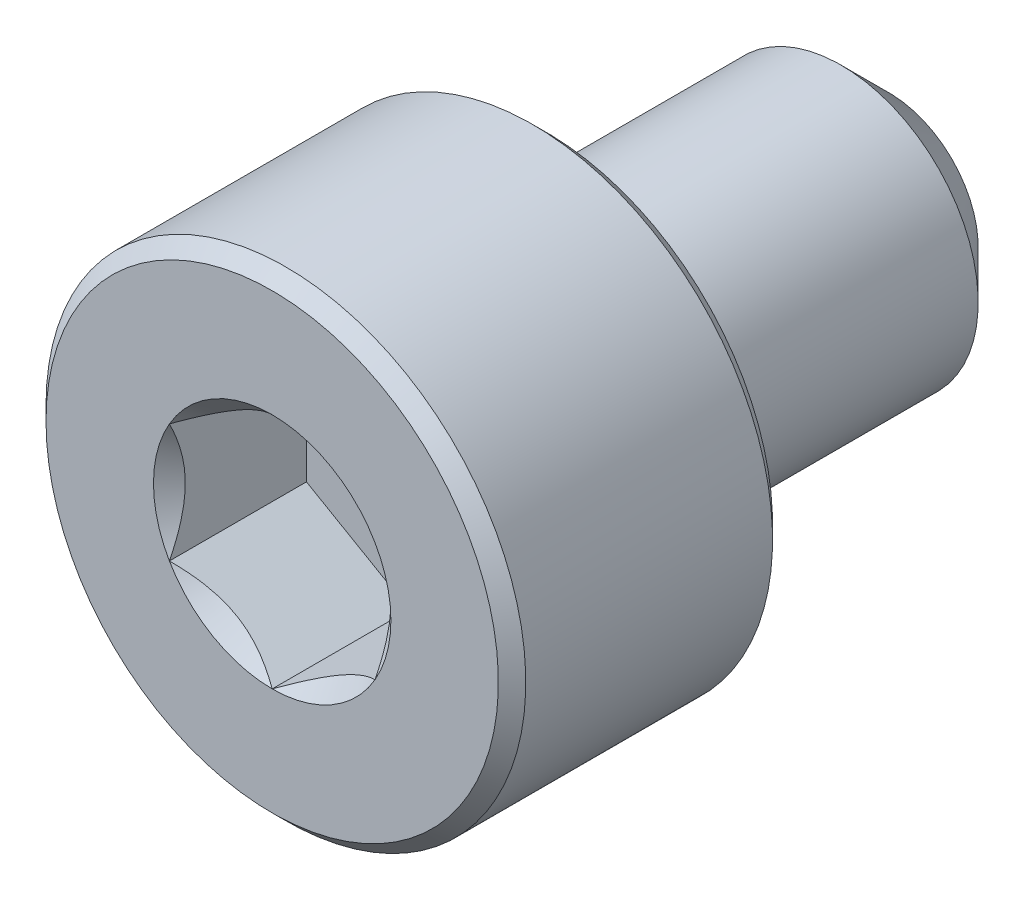
SolidWorks part; units mm, degrees
material "Alloy Steel"
ref_plane "Front Plane" through (0, 0, 0) normal (0, 0, 1) x (1, 0, 0)
ref_plane "Top Plane" through (0, 0, 0) normal (0, 1, 0) x (1, 0, 0)
ref_plane "Right Plane" through (0, 0, 0) normal (1, 0, 0) x (0, 0, -1)
sketch "Sketch1" plane through (0, 0, 0) normal (1, 0, 0) x (0, 0, -1)
  line L0 (-4.5, 0) -> (4.5, 0) construction
  line L1 (4.5, 0) -> (4.5, 1.3) construction
  line L2 (4.5, 1.3) -> (3.8, 2) construction
  line L3 (3.8, 2) -> (-0.5, 2) construction
  line L5 (-0.5, 2) -> (-0.5, 3.5) construction
  line L6 (-0.5, 3.5) -> (-4.5, 3.5) construction
  line L7 (-4.5, 3.5) -> (-4.5, 0) construction
  line L8 (4.5, 1.3) -> (4.5, 2) construction
  line L9 (4.4563, 2.0758) -> (4.8063, 1.4696) construction
  line L10 (4.8063, 1.4696) -> (5.1563, 2.0758) construction
  line L11 (5.1563, 2.0758) -> (4.4563, 2.0758) construction
  line L12 (4.8063, 2.0758) -> (4.8063, 2) construction
  line L13 (4.8063, 1.4696) -> (4.8063, 1.5453) construction
  line L14 (4.7625, 1.5453) -> (4.85, 1.5453) construction
  line L15 (4.5, 2) -> (5.1125, 2) construction
  line L16 (4.4781, 2.0379) -> (5.1344, 2.0379) construction
  line L17 (4.5, 0) -> (4.5, -2) construction
  line L18 (-0.7, 3.5) -> (-0.5, 3.3) construction
  line L19 (-4.3, 3.5) -> (-4.5, 3.3) construction
  point P0 (-4.5, 1.5)
  point P3 (2.05, 2)
  point P4 (0, 0)
  point P22 (4.8063, 1.5453)
  point P24 (-0.5, 2)
  point P25 (4.8063, 2)
  point P28 (4.8063, 2.0379)
  point P29 (2.05, -2)
  point P31 (-2.5, 3.5)
  point P37 (-1.2, 3.5)
  point P38 (-4.2, 3.5)
  point P41 (-2.5, 0)
  dimension "head height" = 4
  dimension "D1" = 45
  dimension "Head Diameter" = 7
  dimension "Thread Size" = 4
  dimension "drive size" = 3
  dimension "Thread Pitch" = 0.7
  dimension "D2" = 0.0875
  dimension "D3" = 0.7
  dimension "D4" = 2.45
  dimension "D7" = 0.2
  dimension "D8" = 0.2
  dimension "D9" = 0.2
  dimension "D10" = 0.1
  dimension "D11" = 0.5
  dimension "length" = 5
  dimension "Drive Depth" = 2
sketch "Sketch2" plane through (0, 0, 0) normal (1, 0, 0) x (0, 0, -1)
  line L1 (-4.3, 3.5) -> (-0.7, 3.5)
  line L4 (3.8, 2) -> (4.5, 1.3)
  line L5 (4.5, 1.3) -> (4.5, 0)
  line L6 (-0.7, 3.5) -> (-0.5, 3.3) construction
  line L7 (4.5, 0) -> (-4.5, 0)
  line L8 (-4.3, 3.5) -> (-4.5, 3.3) construction
  line L9 (-0.7, 3.5) -> (-0.5, 3.3)
  line L10 (-4.3, 3.5) -> (-4.5, 3.3)
  line L11 (-4.5, 3.3) -> (-4.5, 0)
  line L12 (-0.5, 3.3) -> (-0.5, 2)
  line L13 (-0.5, 2) -> (3.8, 2)
revolve "Revolve1" add sketch "Sketch2" angle 360 about L7
sketch "Sketch3" plane through (0, 0, 4.5) normal (0, 0, 1) x (1, 0, 0)
  line L1 (0, 1.7321) -> (-1.5, 0.866)
  line L2 (-1.5, 0.866) -> (-1.5, -0.866)
  line L3 (-1.5, -0.866) -> (0, -1.7321)
  line L4 (0, -1.7321) -> (1.5, -0.866)
  line L5 (1.5, -0.866) -> (1.5, 0.866)
  line L6 (1.5, 0.866) -> (0, 1.7321)
  circle A0 centre (0, 0) radius 1.5 construction
  dimension "D1" = 3
extrude "Cut-Extrude1" cut sketch "Sketch3" against normal up to vertex (2 mm away) up to point (0, 0, 2.5)
sketch "Sketch4" plane through (0, 0, 4.5) normal (0, 0, 1) x (1, 0, 0)
  circle A0 centre (0, 0) radius 1.7321
extrude "Cut-Extrude2" cut sketch "Sketch4" against normal blind 0.5 draft 45
ref_plane "Plane1" [suppressed] through (0, 0, 0.5) normal (0, 0, 1) x (1, 0, 0)
split "Split1" [suppressed] bodies to split 106
sketch "Sketch6" [suppressed] plane through (0, 0, -4.5) normal (0, 0, -1) x (-1, 0, 0)
  circle A0 centre (0, 0) radius 2
curve "Helix/Spiral1" [suppressed] pitch 0.7 height 5.7 turns 8.1429
sketch "Sketch7" [suppressed] plane through (0, 0, 0) normal (1, 0, 0) x (0, 0, -1)
  line L0 (4.4781, 2.0379) -> (5.1344, 2.0379)
  line L1 (5.1344, 2.0379) -> (4.85, 1.5453)
  line L2 (4.85, 1.5453) -> (4.7625, 1.5453)
  line L3 (4.7625, 1.5453) -> (4.4781, 2.0379)
sweep "Cut-Sweep1" [suppressed] cut profiles "Sketch7" path "Helix/Spiral1"
sketch "Sketch8" [suppressed] plane through (0, 0, 0.5) normal (0, 0, -1) x (-1, 0, 0)
  circle A0 centre (0, 0) radius 2
extrude "Boss-Extrude1" [suppressed] add sketch "Sketch8" along normal through all draft 45
ref_plane "Plane2" [suppressed] through (0, 0, 2.5) normal (0, 0, 1) x (1, 0, 0)
sketch "Sketch9" [suppressed] plane through (0, 0, 2.5) normal (0, 0, 1) x (1, 0, 0)
  line L0 (0, 3.4038) -> (0.0916, 3.4988)
  line L1 (0, 3.4038) -> (-0.0916, 3.4988)
  line L2 (0, 3.5) -> (0, 0) construction
  line L3 (-0.0916, 3.4988) -> (0, 0) construction
  line L4 (0, 0) -> (0.0916, 3.4988) construction
  arc A0 (0.0916, 3.4988) -> (-0.0916, 3.4988) centre (0, 0) ccw
  circle A1 centre (0, 0) radius 3.4038 construction
  dimension "D1" = 7
  dimension "D2" = 6.8075
  dimension "D3" = 3
extrude "Cut-Extrude4" [suppressed] cut sketch "Sketch9" against normal up to vertex and the other way up to vertex up to point (0, 3.5, 1.2) other way up to point (0, 3.5, 4.2)
pattern_circular "CirPattern2" [suppressed] count 96 over 360 about axis through (0, 0, 4.5) along (0, 0, -1) of bodies 113
equation "\"D2@Sketch1\" = \"Thread Pitch@Sketch1\" / 8"
equation "\"D3@Sketch1\" = \"Thread Pitch@Sketch1\""
equation "\"D3@Helix/Spiral1\" = \"length@Sketch1\" + \"Thread Pitch@Sketch1\""
equation "\"D4@Helix/Spiral1\" = \"Thread Pitch@Sketch1\""
equation "\"D4@Sketch1\" = \"Thread Pitch@Sketch1\" * 3.5"
equation "\"D7@Sketch1\"=\"head height@Sketch1\"*.05"
equation "\"D8@Sketch1\"=\"D7@Sketch1\""
equation "\"D9@Sketch1\"=\"D7@Sketch1\""
equation "\"D10@Sketch1\"=\"D7@Sketch1\"/2"
equation "\"D11@Sketch1\"=\"D10@Sketch1\"*5"
equation "\"D1@CirPattern2\"=( 360 / \"D3@Sketch9\" )*0.8"
equation "\"D1@Sketch3\" = \"drive size@Sketch1\""
equation "\"D2@Sketch9\"=\"Head Diameter@Sketch1\" * 0.9725"
